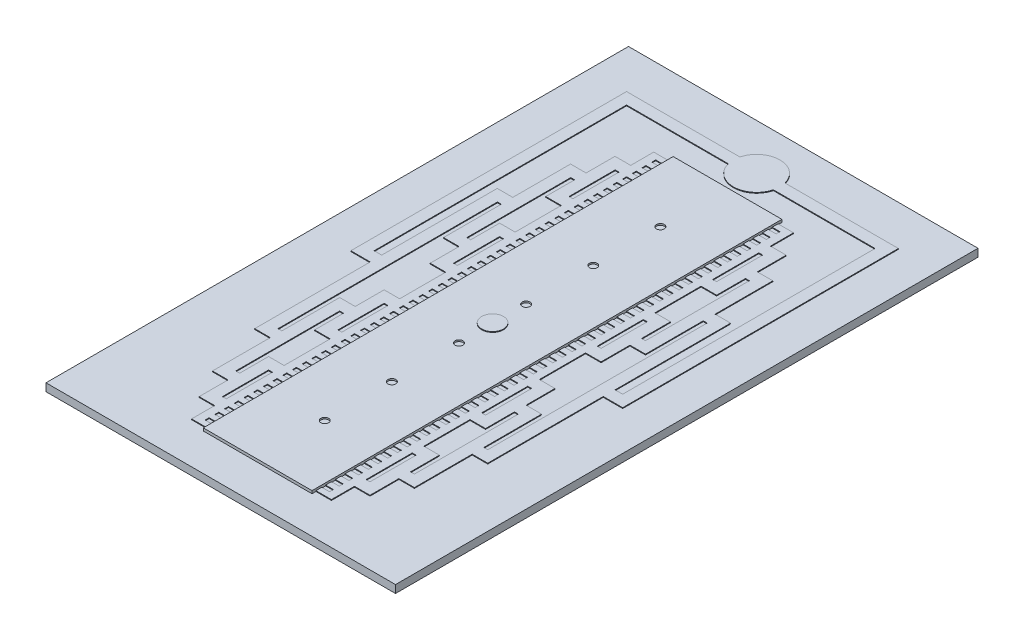
SolidWorks part; units mm, degrees
ref_plane "Front Plane" through (0, 0, 0) normal (0, 0, 1) x (1, 0, 0)
ref_plane "Top Plane" through (0, 0, 0) normal (0, 1, 0) x (1, 0, 0)
ref_plane "Right Plane" through (0, 0, 0) normal (1, 0, 0) x (0, 0, -1)
sketch "Sketch2" plane through (0, 0, 0) normal (0, 1, 0) x (1, 0, 0)
  line L1 (-22.5, 37.5) -> (22.5, 37.5)
  line L2 (-22.5, 37.5) -> (-22.5, -37.5)
  line L3 (-22.5, -37.5) -> (22.5, -37.5)
  line L4 (22.5, 37.5) -> (22.5, -37.5)
  line L5 (-22.5, 37.5) -> (22.5, -37.5) construction
  line L6 (-22.5, -37.5) -> (22.5, 37.5) construction
  point P0 (0, 0)
extrude "Boss-Extrude1" add sketch "Sketch2" along normal blind 1
sketch "Sketch3" plane through (0, 1, 0) normal (0, 1, 0) x (1, 0, 0)
  line L1 (-7, 30.25) -> (7, 30.25)
  line L2 (-7, 30.25) -> (-7, -30.25)
  line L3 (-7, -30.25) -> (7, -30.25)
  line L4 (7, 30.25) -> (7, -30.25)
  line L5 (-7, 30.25) -> (7, -30.25) construction
  line L6 (-7, -30.25) -> (7, 30.25) construction
  point P0 (0, 0)
extrude "Boss-Extrude2" add sketch "Sketch3" along normal blind 0.35
sketch "Sketch4" plane through (0, 1, 0) normal (0, 1, 0) x (1, 0, 0)
  line L0 (7, 29.75) -> (9, 29.75)
  line L1 (7, 29.75) -> (7, -29.75)
  line L2 (9, 29.75) -> (9, -29.75)
  line L3 (7, -29.75) -> (9, -29.75)
  line L4 (7, -30.25) -> (7, 30.25) construction
  line L5 (0, 31.7119) -> (0, -31.7119) construction
  line L6 (-9, 29.75) -> (-9, -29.75)
  line L7 (-7, -29.75) -> (-9, -29.75)
  line L8 (-7, 29.75) -> (-7, -29.75)
  line L9 (-7, 29.75) -> (-9, 29.75)
  point P6 (9, 0)
  point P11 (0, 0)
extrude "Boss-Extrude3" add sketch "Sketch4" along normal blind 0.1
sketch "Sketch5" plane through (0, 1.1, 0) normal (0, 1, 0) x (1, 0, 0)
  line L0 (7, 29) -> (8, 29)
  line L1 (7, 29) -> (7, 28.5)
  line L2 (8, 29) -> (8, 28.5)
  line L3 (7, 28.5) -> (8, 28.5)
  line L4 (7, -30.25) -> (7, 30.25) construction
  line L5 (-8, 29) -> (-7, 29)
  line L6 (-8, 29) -> (-8, 28.5)
  line L7 (-8, 28.5) -> (-7, 28.5)
  line L8 (-7, 29) -> (-7, 28.5)
  line L9 (-8, 27.75) -> (-7, 27.75)
  line L10 (-8, 27.75) -> (-8, 27.25)
  line L11 (-8, 27.25) -> (-7, 27.25)
  line L12 (-7, 27.75) -> (-7, 27.25)
  line L13 (-8, 26.5) -> (-7, 26.5)
  line L14 (-8, 26.5) -> (-8, 26)
  line L15 (-8, 26) -> (-7, 26)
  line L16 (-7, 26.5) -> (-7, 26)
  line L17 (-8, 25.25) -> (-7, 25.25)
  line L18 (-8, 25.25) -> (-8, 24.75)
  line L19 (-8, 24.75) -> (-7, 24.75)
  line L20 (-7, 25.25) -> (-7, 24.75)
  line L21 (-8, 24) -> (-7, 24)
  line L22 (-8, 24) -> (-8, 23.5)
  line L23 (-8, 23.5) -> (-7, 23.5)
  line L24 (-7, 24) -> (-7, 23.5)
  line L25 (-8, 22.75) -> (-7, 22.75)
  line L26 (-8, 22.75) -> (-8, 22.25)
  line L27 (-8, 22.25) -> (-7, 22.25)
  line L28 (-7, 22.75) -> (-7, 22.25)
  line L29 (-8, 21.5) -> (-7, 21.5)
  line L30 (-8, 21.5) -> (-8, 21)
  line L31 (-8, 21) -> (-7, 21)
  line L32 (-7, 21.5) -> (-7, 21)
  line L33 (-8, 20.25) -> (-7, 20.25)
  line L34 (-8, 20.25) -> (-8, 19.75)
  line L35 (-8, 19.75) -> (-7, 19.75)
  line L36 (-7, 20.25) -> (-7, 19.75)
  line L37 (-8, 19) -> (-7, 19)
  line L38 (-8, 19) -> (-8, 18.5)
  line L39 (-8, 18.5) -> (-7, 18.5)
  line L40 (-7, 19) -> (-7, 18.5)
  line L41 (-8, 17.75) -> (-7, 17.75)
  line L42 (-8, 17.75) -> (-8, 17.25)
  line L43 (-8, 17.25) -> (-7, 17.25)
  line L44 (-7, 17.75) -> (-7, 17.25)
  line L45 (-8, 16.5) -> (-7, 16.5)
  line L46 (-8, 16.5) -> (-8, 16)
  line L47 (-8, 16) -> (-7, 16)
  line L48 (-7, 16.5) -> (-7, 16)
  line L49 (-8, 15.25) -> (-7, 15.25)
  line L50 (-8, 15.25) -> (-8, 14.75)
  line L51 (-8, 14.75) -> (-7, 14.75)
  line L52 (-7, 15.25) -> (-7, 14.75)
  line L53 (-8, 14) -> (-7, 14)
  line L54 (-8, 14) -> (-8, 13.5)
  line L55 (-8, 13.5) -> (-7, 13.5)
  line L56 (-7, 14) -> (-7, 13.5)
  line L57 (-8, 12.75) -> (-7, 12.75)
  line L58 (-8, 12.75) -> (-8, 12.25)
  line L59 (-8, 12.25) -> (-7, 12.25)
  line L60 (-7, 12.75) -> (-7, 12.25)
  line L61 (-8, 11.5) -> (-7, 11.5)
  line L62 (-8, 11.5) -> (-8, 11)
  line L63 (-8, 11) -> (-7, 11)
  line L64 (-7, 11.5) -> (-7, 11)
  line L65 (-8, 10.25) -> (-7, 10.25)
  line L66 (-8, 10.25) -> (-8, 9.75)
  line L67 (-8, 9.75) -> (-7, 9.75)
  line L68 (-7, 10.25) -> (-7, 9.75)
  line L69 (-8, 9) -> (-7, 9)
  line L70 (-8, 9) -> (-8, 8.5)
  line L71 (-8, 8.5) -> (-7, 8.5)
  line L72 (-7, 9) -> (-7, 8.5)
  line L73 (-8, 7.75) -> (-7, 7.75)
  line L74 (-8, 7.75) -> (-8, 7.25)
  line L75 (-8, 7.25) -> (-7, 7.25)
  line L76 (-7, 7.75) -> (-7, 7.25)
  line L77 (-8, 6.5) -> (-7, 6.5)
  line L78 (-8, 6.5) -> (-8, 6)
  line L79 (-8, 6) -> (-7, 6)
  line L80 (-7, 6.5) -> (-7, 6)
  line L81 (-8, 5.25) -> (-7, 5.25)
  line L82 (-8, 5.25) -> (-8, 4.75)
  line L83 (-8, 4.75) -> (-7, 4.75)
  line L84 (-7, 5.25) -> (-7, 4.75)
  line L85 (-8, 4) -> (-7, 4)
  line L86 (-8, 4) -> (-8, 3.5)
  line L87 (-8, 3.5) -> (-7, 3.5)
  line L88 (-7, 4) -> (-7, 3.5)
  line L89 (-8, 2.75) -> (-7, 2.75)
  line L90 (-8, 2.75) -> (-8, 2.25)
  line L91 (-8, 2.25) -> (-7, 2.25)
  line L92 (-7, 2.75) -> (-7, 2.25)
  line L93 (-8, 1.5) -> (-7, 1.5)
  line L94 (-8, 1.5) -> (-8, 1)
  line L95 (-8, 1) -> (-7, 1)
  line L96 (-7, 1.5) -> (-7, 1)
  line L97 (-8, 0.25) -> (-7, 0.25)
  line L98 (-8, 0.25) -> (-8, -0.25)
  line L99 (-8, -0.25) -> (-7, -0.25)
  line L100 (-7, 0.25) -> (-7, -0.25)
  line L101 (-8, -1) -> (-7, -1)
  line L102 (-8, -1) -> (-8, -1.5)
  line L103 (-8, -1.5) -> (-7, -1.5)
  line L104 (-7, -1) -> (-7, -1.5)
  line L105 (-8, -2.25) -> (-7, -2.25)
  line L106 (-8, -2.25) -> (-8, -2.75)
  line L107 (-8, -2.75) -> (-7, -2.75)
  line L108 (-7, -2.25) -> (-7, -2.75)
  line L109 (-8, -3.5) -> (-7, -3.5)
  line L110 (-8, -3.5) -> (-8, -4)
  line L111 (-8, -4) -> (-7, -4)
  line L112 (-7, -3.5) -> (-7, -4)
  line L113 (-8, -4.75) -> (-7, -4.75)
  line L114 (-8, -4.75) -> (-8, -5.25)
  line L115 (-8, -5.25) -> (-7, -5.25)
  line L116 (-7, -4.75) -> (-7, -5.25)
  line L117 (-8, -6) -> (-7, -6)
  line L118 (-8, -6) -> (-8, -6.5)
  line L119 (-8, -6.5) -> (-7, -6.5)
  line L120 (-7, -6) -> (-7, -6.5)
  line L121 (-8, -7.25) -> (-7, -7.25)
  line L122 (-8, -7.25) -> (-8, -7.75)
  line L123 (-8, -7.75) -> (-7, -7.75)
  line L124 (-7, -7.25) -> (-7, -7.75)
  line L125 (-8, -8.5) -> (-7, -8.5)
  line L126 (-8, -8.5) -> (-8, -9)
  line L127 (-8, -9) -> (-7, -9)
  line L128 (-7, -8.5) -> (-7, -9)
  line L129 (-8, -9.75) -> (-7, -9.75)
  line L130 (-8, -9.75) -> (-8, -10.25)
  line L131 (-8, -10.25) -> (-7, -10.25)
  line L132 (-7, -9.75) -> (-7, -10.25)
  line L133 (-8, -11) -> (-7, -11)
  line L134 (-8, -11) -> (-8, -11.5)
  line L135 (-8, -11.5) -> (-7, -11.5)
  line L136 (-7, -11) -> (-7, -11.5)
  line L137 (-8, -12.25) -> (-7, -12.25)
  line L138 (-8, -12.25) -> (-8, -12.75)
  line L139 (-8, -12.75) -> (-7, -12.75)
  line L140 (-7, -12.25) -> (-7, -12.75)
  line L141 (-8, -13.5) -> (-7, -13.5)
  line L142 (-8, -13.5) -> (-8, -14)
  line L143 (-8, -14) -> (-7, -14)
  line L144 (-7, -13.5) -> (-7, -14)
  line L145 (-8, -14.75) -> (-7, -14.75)
  line L146 (-8, -14.75) -> (-8, -15.25)
  line L147 (-8, -15.25) -> (-7, -15.25)
  line L148 (-7, -14.75) -> (-7, -15.25)
  line L149 (-8, -16) -> (-7, -16)
  line L150 (-8, -16) -> (-8, -16.5)
  line L151 (-8, -16.5) -> (-7, -16.5)
  line L152 (-7, -16) -> (-7, -16.5)
  line L153 (-8, -17.25) -> (-7, -17.25)
  line L154 (-8, -17.25) -> (-8, -17.75)
  line L155 (-8, -17.75) -> (-7, -17.75)
  line L156 (-7, -17.25) -> (-7, -17.75)
  line L157 (-8, -18.5) -> (-7, -18.5)
  line L158 (-8, -18.5) -> (-8, -19)
  line L159 (-8, -19) -> (-7, -19)
  line L160 (-7, -18.5) -> (-7, -19)
  line L161 (-8, -19.75) -> (-7, -19.75)
  line L162 (-8, -19.75) -> (-8, -20.25)
  line L163 (-8, -20.25) -> (-7, -20.25)
  line L164 (-7, -19.75) -> (-7, -20.25)
  line L165 (-8, -21) -> (-7, -21)
  line L166 (-8, -21) -> (-8, -21.5)
  line L167 (-8, -21.5) -> (-7, -21.5)
  line L168 (-7, -21) -> (-7, -21.5)
  line L169 (-8, -22.25) -> (-7, -22.25)
  line L170 (-8, -22.25) -> (-8, -22.75)
  line L171 (-8, -22.75) -> (-7, -22.75)
  line L172 (-7, -22.25) -> (-7, -22.75)
  line L173 (-8, -23.5) -> (-7, -23.5)
  line L174 (-8, -23.5) -> (-8, -24)
  line L175 (-8, -24) -> (-7, -24)
  line L176 (-7, -23.5) -> (-7, -24)
  line L177 (-8, -24.75) -> (-7, -24.75)
  line L178 (-8, -24.75) -> (-8, -25.25)
  line L179 (-8, -25.25) -> (-7, -25.25)
  line L180 (-7, -24.75) -> (-7, -25.25)
  line L181 (-8, -26) -> (-7, -26)
  line L182 (-8, -26) -> (-8, -26.5)
  line L183 (-8, -26.5) -> (-7, -26.5)
  line L184 (-7, -26) -> (-7, -26.5)
  line L185 (-8, -27.25) -> (-7, -27.25)
  line L186 (-8, -27.25) -> (-8, -27.75)
  line L187 (-8, -27.75) -> (-7, -27.75)
  line L188 (-7, -27.25) -> (-7, -27.75)
  line L189 (-8, -28.5) -> (-7, -28.5)
  line L190 (-8, -28.5) -> (-8, -29)
  line L191 (-8, -29) -> (-7, -29)
  line L192 (-7, -28.5) -> (-7, -29)
  line L193 (7, 27.75) -> (8, 27.75)
  line L194 (7, 27.75) -> (7, 27.25)
  line L195 (7, 27.25) -> (8, 27.25)
  line L196 (8, 27.75) -> (8, 27.25)
  line L197 (7, 26.5) -> (8, 26.5)
  line L198 (7, 26.5) -> (7, 26)
  line L199 (7, 26) -> (8, 26)
  line L200 (8, 26.5) -> (8, 26)
  line L201 (7, 25.25) -> (8, 25.25)
  line L202 (7, 25.25) -> (7, 24.75)
  line L203 (7, 24.75) -> (8, 24.75)
  line L204 (8, 25.25) -> (8, 24.75)
  line L205 (7, 24) -> (8, 24)
  line L206 (7, 24) -> (7, 23.5)
  line L207 (7, 23.5) -> (8, 23.5)
  line L208 (8, 24) -> (8, 23.5)
  line L209 (7, 22.75) -> (8, 22.75)
  line L210 (7, 22.75) -> (7, 22.25)
  line L211 (7, 22.25) -> (8, 22.25)
  line L212 (8, 22.75) -> (8, 22.25)
  line L213 (7, 21.5) -> (8, 21.5)
  line L214 (7, 21.5) -> (7, 21)
  line L215 (7, 21) -> (8, 21)
  line L216 (8, 21.5) -> (8, 21)
  line L217 (7, 20.25) -> (8, 20.25)
  line L218 (7, 20.25) -> (7, 19.75)
  line L219 (7, 19.75) -> (8, 19.75)
  line L220 (8, 20.25) -> (8, 19.75)
  line L221 (7, 19) -> (8, 19)
  line L222 (7, 19) -> (7, 18.5)
  line L223 (7, 18.5) -> (8, 18.5)
  line L224 (8, 19) -> (8, 18.5)
  line L225 (7, 17.75) -> (8, 17.75)
  line L226 (7, 17.75) -> (7, 17.25)
  line L227 (7, 17.25) -> (8, 17.25)
  line L228 (8, 17.75) -> (8, 17.25)
  line L229 (7, 16.5) -> (8, 16.5)
  line L230 (7, 16.5) -> (7, 16)
  line L231 (7, 16) -> (8, 16)
  line L232 (8, 16.5) -> (8, 16)
  line L233 (7, 15.25) -> (8, 15.25)
  line L234 (7, 15.25) -> (7, 14.75)
  line L235 (7, 14.75) -> (8, 14.75)
  line L236 (8, 15.25) -> (8, 14.75)
  line L237 (7, 14) -> (8, 14)
  line L238 (7, 14) -> (7, 13.5)
  line L239 (7, 13.5) -> (8, 13.5)
  line L240 (8, 14) -> (8, 13.5)
  line L241 (7, 12.75) -> (8, 12.75)
  line L242 (7, 12.75) -> (7, 12.25)
  line L243 (7, 12.25) -> (8, 12.25)
  line L244 (8, 12.75) -> (8, 12.25)
  line L245 (7, 11.5) -> (8, 11.5)
  line L246 (7, 11.5) -> (7, 11)
  line L247 (7, 11) -> (8, 11)
  line L248 (8, 11.5) -> (8, 11)
  line L249 (7, 10.25) -> (8, 10.25)
  line L250 (7, 10.25) -> (7, 9.75)
  line L251 (7, 9.75) -> (8, 9.75)
  line L252 (8, 10.25) -> (8, 9.75)
  line L253 (7, 9) -> (8, 9)
  line L254 (7, 9) -> (7, 8.5)
  line L255 (7, 8.5) -> (8, 8.5)
  line L256 (8, 9) -> (8, 8.5)
  line L257 (7, 7.75) -> (8, 7.75)
  line L258 (7, 7.75) -> (7, 7.25)
  line L259 (7, 7.25) -> (8, 7.25)
  line L260 (8, 7.75) -> (8, 7.25)
  line L261 (7, 6.5) -> (8, 6.5)
  line L262 (7, 6.5) -> (7, 6)
  line L263 (7, 6) -> (8, 6)
  line L264 (8, 6.5) -> (8, 6)
  line L265 (7, 5.25) -> (8, 5.25)
  line L266 (7, 5.25) -> (7, 4.75)
  line L267 (7, 4.75) -> (8, 4.75)
  line L268 (8, 5.25) -> (8, 4.75)
  line L269 (7, 4) -> (8, 4)
  line L270 (7, 4) -> (7, 3.5)
  line L271 (7, 3.5) -> (8, 3.5)
  line L272 (8, 4) -> (8, 3.5)
  line L273 (7, 2.75) -> (8, 2.75)
  line L274 (7, 2.75) -> (7, 2.25)
  line L275 (7, 2.25) -> (8, 2.25)
  line L276 (8, 2.75) -> (8, 2.25)
  line L277 (7, 1.5) -> (8, 1.5)
  line L278 (7, 1.5) -> (7, 1)
  line L279 (7, 1) -> (8, 1)
  line L280 (8, 1.5) -> (8, 1)
  line L281 (7, 0.25) -> (8, 0.25)
  line L282 (7, 0.25) -> (7, -0.25)
  line L283 (7, -0.25) -> (8, -0.25)
  line L284 (8, 0.25) -> (8, -0.25)
  line L285 (7, -1) -> (8, -1)
  line L286 (7, -1) -> (7, -1.5)
  line L287 (7, -1.5) -> (8, -1.5)
  line L288 (8, -1) -> (8, -1.5)
  line L289 (7, -2.25) -> (8, -2.25)
  line L290 (7, -2.25) -> (7, -2.75)
  line L291 (7, -2.75) -> (8, -2.75)
  line L292 (8, -2.25) -> (8, -2.75)
  line L293 (7, -3.5) -> (8, -3.5)
  line L294 (7, -3.5) -> (7, -4)
  line L295 (7, -4) -> (8, -4)
  line L296 (8, -3.5) -> (8, -4)
  line L297 (7, -4.75) -> (8, -4.75)
  line L298 (7, -4.75) -> (7, -5.25)
  line L299 (7, -5.25) -> (8, -5.25)
  line L300 (8, -4.75) -> (8, -5.25)
  line L301 (7, -6) -> (8, -6)
  line L302 (7, -6) -> (7, -6.5)
  line L303 (7, -6.5) -> (8, -6.5)
  line L304 (8, -6) -> (8, -6.5)
  line L305 (7, -7.25) -> (8, -7.25)
  line L306 (7, -7.25) -> (7, -7.75)
  line L307 (7, -7.75) -> (8, -7.75)
  line L308 (8, -7.25) -> (8, -7.75)
  line L309 (7, -8.5) -> (8, -8.5)
  line L310 (7, -8.5) -> (7, -9)
  line L311 (7, -9) -> (8, -9)
  line L312 (8, -8.5) -> (8, -9)
  line L313 (7, -9.75) -> (8, -9.75)
  line L314 (7, -9.75) -> (7, -10.25)
  line L315 (7, -10.25) -> (8, -10.25)
  line L316 (8, -9.75) -> (8, -10.25)
  line L317 (7, -11) -> (8, -11)
  line L318 (7, -11) -> (7, -11.5)
  line L319 (7, -11.5) -> (8, -11.5)
  line L320 (8, -11) -> (8, -11.5)
  line L321 (7, -12.25) -> (8, -12.25)
  line L322 (7, -12.25) -> (7, -12.75)
  line L323 (7, -12.75) -> (8, -12.75)
  line L324 (8, -12.25) -> (8, -12.75)
  line L325 (7, -13.5) -> (8, -13.5)
  line L326 (7, -13.5) -> (7, -14)
  line L327 (7, -14) -> (8, -14)
  line L328 (8, -13.5) -> (8, -14)
  line L329 (7, -14.75) -> (8, -14.75)
  line L330 (7, -14.75) -> (7, -15.25)
  line L331 (7, -15.25) -> (8, -15.25)
  line L332 (8, -14.75) -> (8, -15.25)
  line L333 (7, -16) -> (8, -16)
  line L334 (7, -16) -> (7, -16.5)
  line L335 (7, -16.5) -> (8, -16.5)
  line L336 (8, -16) -> (8, -16.5)
  line L337 (7, -17.25) -> (8, -17.25)
  line L338 (7, -17.25) -> (7, -17.75)
  line L339 (7, -17.75) -> (8, -17.75)
  line L340 (8, -17.25) -> (8, -17.75)
  line L341 (7, -18.5) -> (8, -18.5)
  line L342 (7, -18.5) -> (7, -19)
  line L343 (7, -19) -> (8, -19)
  line L344 (8, -18.5) -> (8, -19)
  line L345 (7, -19.75) -> (8, -19.75)
  line L346 (7, -19.75) -> (7, -20.25)
  line L347 (7, -20.25) -> (8, -20.25)
  line L348 (8, -19.75) -> (8, -20.25)
  line L349 (7, -21) -> (8, -21)
  line L350 (7, -21) -> (7, -21.5)
  line L351 (7, -21.5) -> (8, -21.5)
  line L352 (8, -21) -> (8, -21.5)
  line L353 (7, -22.25) -> (8, -22.25)
  line L354 (7, -22.25) -> (7, -22.75)
  line L355 (7, -22.75) -> (8, -22.75)
  line L356 (8, -22.25) -> (8, -22.75)
  line L357 (7, -23.5) -> (8, -23.5)
  line L358 (7, -23.5) -> (7, -24)
  line L359 (7, -24) -> (8, -24)
  line L360 (8, -23.5) -> (8, -24)
  line L361 (7, -24.75) -> (8, -24.75)
  line L362 (7, -24.75) -> (7, -25.25)
  line L363 (7, -25.25) -> (8, -25.25)
  line L364 (8, -24.75) -> (8, -25.25)
  line L365 (7, -26) -> (8, -26)
  line L366 (7, -26) -> (7, -26.5)
  line L367 (7, -26.5) -> (8, -26.5)
  line L368 (8, -26) -> (8, -26.5)
  line L369 (7, -27.25) -> (8, -27.25)
  line L370 (7, -27.25) -> (7, -27.75)
  line L371 (7, -27.75) -> (8, -27.75)
  line L372 (8, -27.25) -> (8, -27.75)
  line L373 (7, -28.5) -> (8, -28.5)
  line L374 (7, -28.5) -> (7, -29)
  line L375 (7, -29) -> (8, -29)
  line L376 (8, -28.5) -> (8, -29)
  dimension "D1" = 0.75
  dimension "D2" = 2
  dimension "D3" = 47
extrude "Cut-Extrude1" cut sketch "Sketch5" against normal blind 0.1
sketch "Sketch6" plane through (0, 1, 0) normal (0, 1, 0) x (1, 0, 0)
  line L0 (0, -32.9565) -> (0, 32.9565) construction
  line L1 (-17.9872, 0) -> (17.9872, 0) construction
  line L2 (7, 30.25) -> (-7, 30.25) construction
  line L3 (-17.5, 34.75) -> (17.5, 34.75)
  line L4 (-16, 33.25) -> (16, 33.25)
  line L5 (-17.5, 34.75) -> (-17.5, -0.75)
  line L6 (-16, 33.25) -> (-16, 0.75)
  line L7 (-17.5, -0.75) -> (-15, -0.75)
  line L8 (-16, 0.75) -> (-15.0229, 0.75)
  line L9 (-9, 29.75) -> (-9, -29.75) construction
  line L10 (-9, 26.7813) -> (-11.0229, 26.7813)
  line L11 (-9, 25.2813) -> (-9.5, 25.2813)
  line L12 (-9, 17.8438) -> (-11, 17.8438)
  line L13 (-9, 19.3438) -> (-9.5, 19.3438)
  line L14 (-9.5, 19.3438) -> (-9.5, 25.2813)
  line L15 (-11.0229, 23.0625) -> (-11.0229, 26.7813)
  line L16 (-11, 21.5625) -> (-11, 17.8438)
  line L17 (-9, 29.75) -> (-9, -29.75) construction
  line L18 (-9, 2.9688) -> (-11, 2.9688)
  line L19 (-9, 4.4688) -> (-9.5, 4.4688)
  line L20 (-9, 11.9063) -> (-11, 11.9063)
  line L21 (-9, 10.4063) -> (-9.5, 10.4063)
  line L22 (-9.5, 10.4063) -> (-9.5, 4.4688)
  line L23 (-11, 2.9688) -> (-11, 6.6875)
  line L24 (-11, 8.1875) -> (-11, 11.9063)
  line L25 (-9, -2.9687) -> (-11, -2.9687)
  line L26 (-9, -4.4687) -> (-9.5, -4.4687)
  line L27 (-9, -11.9062) -> (-11, -11.9062)
  line L28 (-9, -10.4062) -> (-9.5, -10.4062)
  line L29 (-9.5, -10.4062) -> (-9.5, -4.4687)
  line L30 (-11, -11.9062) -> (-11, -8.1875)
  line L31 (-9, -17.8437) -> (-11, -17.8437)
  line L32 (-11, -6.6875) -> (-11, -2.9687)
  line L33 (-9, -19.3437) -> (-9.5, -19.3437)
  line L34 (-9, -26.7812) -> (-11, -26.7812)
  line L35 (-9, -25.2812) -> (-9.5, -25.2812)
  line L36 (-9.5, -25.2812) -> (-9.5, -19.3437)
  line L37 (-11, -17.8437) -> (-11, -21.5625)
  line L38 (-11, -23.0625) -> (-11, -26.7812)
  line L39 (-9, -22.3125) -> (-11.344, -22.3125) construction
  line L40 (-9, -7.4375) -> (-11.3125, -7.4375) construction
  line L41 (-9, 7.4375) -> (-11.3125, 7.4375) construction
  line L42 (-9, 22.3125) -> (-11.3125, 22.3125) construction
  line L43 (-11.0229, 23.0625) -> (-13.0229, 23.0625)
  line L44 (-11, 21.5625) -> (-11.5, 21.5625)
  line L45 (-11, 6.6875) -> (-13, 6.6875)
  line L46 (-11, 8.1875) -> (-11.5, 8.1875)
  line L47 (-11.5, 8.1875) -> (-11.5, 21.5625)
  line L48 (-13.0229, 23.0625) -> (-13.0229, 15.625)
  line L49 (-13, 14.125) -> (-13, 6.6875)
  line L50 (-11, -6.6875) -> (-13, -6.6875)
  line L51 (-11, -8.1875) -> (-11.5, -8.1875)
  line L52 (-11, -23.0625) -> (-13, -23.0625)
  line L53 (-11, -21.5625) -> (-11.5, -21.5625)
  line L54 (-11.5, -21.5625) -> (-11.5, -8.1875)
  line L55 (-13, -6.6875) -> (-13, -14.125)
  line L56 (-13, -15.625) -> (-13, -23.0625)
  line L57 (-9, 14.875) -> (-13.3781, 14.875) construction
  line L58 (-9, -14.875) -> (-13.151, -14.875) construction
  line L59 (-13, -15.625) -> (-15, -15.625)
  line L60 (-13, -14.125) -> (-13.5, -14.125)
  line L61 (-13.0229, 15.625) -> (-15.0229, 15.625)
  line L62 (-13, 14.125) -> (-13.5, 14.125)
  line L63 (-13.5, 14.125) -> (-13.5, -14.125)
  line L64 (-15, -15.625) -> (-15, -0.75)
  line L65 (-15.0229, 0.75) -> (-15.0229, 15.625)
  line L66 (9, 25.2813) -> (9.5, 25.2813)
  line L67 (11.0229, 23.0625) -> (11.0229, 26.7813)
  line L68 (9, 26.7813) -> (11.0229, 26.7813)
  line L69 (11.0229, 23.0625) -> (13.0229, 23.0625)
  line L70 (11, 21.5625) -> (11.5, 21.5625)
  line L71 (9.5, 19.3438) -> (9.5, 25.2813)
  line L72 (9, 19.3438) -> (9.5, 19.3438)
  line L73 (11, 21.5625) -> (11, 17.8438)
  line L74 (9, 17.8438) -> (11, 17.8438)
  line L75 (13.0229, 23.0625) -> (13.0229, 15.625)
  line L76 (13, 14.125) -> (13.5, 14.125)
  line L77 (13.0229, 15.625) -> (15.0229, 15.625)
  line L78 (9, 10.4063) -> (9.5, 10.4063)
  line L79 (9, 11.9063) -> (11, 11.9063)
  line L80 (11, 8.1875) -> (11, 11.9063)
  line L81 (11.5, 8.1875) -> (11.5, 21.5625)
  line L82 (11, 8.1875) -> (11.5, 8.1875)
  line L83 (13, 14.125) -> (13, 6.6875)
  line L84 (11, 6.6875) -> (13, 6.6875)
  line L85 (9, 4.4688) -> (9.5, 4.4688)
  line L86 (9.5, 10.4063) -> (9.5, 4.4688)
  line L87 (11, 2.9688) -> (11, 6.6875)
  line L88 (9, 2.9688) -> (11, 2.9688)
  line L89 (17.5, 34.75) -> (17.5, -0.75)
  line L90 (15.0229, 0.75) -> (15.0229, 15.625)
  line L91 (16, 33.25) -> (16, 0.75)
  line L92 (16, 0.75) -> (15.0229, 0.75)
  line L93 (17.5, -0.75) -> (15, -0.75)
  line L94 (9, -2.9687) -> (11, -2.9687)
  line L95 (9, -10.4062) -> (9.5, -10.4062)
  line L96 (9, -4.4687) -> (9.5, -4.4687)
  line L97 (11, -6.6875) -> (11, -2.9687)
  line L98 (11, -6.6875) -> (13, -6.6875)
  line L99 (11, -8.1875) -> (11.5, -8.1875)
  line L100 (9.5, -10.4062) -> (9.5, -4.4687)
  line L101 (11, -11.9062) -> (11, -8.1875)
  line L102 (9, -11.9062) -> (11, -11.9062)
  line L103 (13, -6.6875) -> (13, -14.125)
  line L104 (15, -15.625) -> (15, -0.75)
  line L105 (13.5, 14.125) -> (13.5, -14.125)
  line L106 (13, -15.625) -> (15, -15.625)
  line L107 (13, -14.125) -> (13.5, -14.125)
  line L108 (9, -17.8437) -> (11, -17.8437)
  line L109 (9, -19.3437) -> (9.5, -19.3437)
  line L110 (11, -17.8437) -> (11, -21.5625)
  line L111 (11.5, -21.5625) -> (11.5, -8.1875)
  line L112 (13, -15.625) -> (13, -23.0625)
  line L113 (11, -23.0625) -> (13, -23.0625)
  line L114 (11, -21.5625) -> (11.5, -21.5625)
  line L115 (9.5, -25.2812) -> (9.5, -19.3437)
  line L116 (11, -23.0625) -> (11, -26.7812)
  line L117 (9, -26.7812) -> (11, -26.7812)
  line L118 (9, -25.2812) -> (9.5, -25.2812)
  circle A0 centre (0, 34) radius 3
  point P0 (0, 30.25)
  point P4 (0, 0)
  point P8 (0, 0)
  point P9 (0, 34)
  point P14 (0, 33.25)
  point P15 (0, 34.75)
  point P16 (-16, 0)
  point P19 (0, 34.75)
  point P22 (0, 33.25)
  point P24 (-17.5, 0)
  point P26 (-9, 29.75)
  point P29 (-9, 26.7813)
  point P31 (-9, 25.2813)
  point P32 (-9, 26.0313)
  point P33 (-9, 22.3125)
  point P34 (-9, 18.5938)
  point P35 (-9, 14.875)
  point P36 (-9, 11.1563)
  point P37 (-9, 7.4375)
  point P38 (-9, 3.7188)
  point P39 (-9, 0)
  point P40 (-9, -3.7187)
  point P41 (-9, -7.4375)
  point P42 (-9, -11.1562)
  point P43 (-9, -14.875)
  point P44 (-9, -18.5937)
  point P45 (-9, -22.3125)
  point P46 (-9, -26.0312)
  point P47 (-9, -29.75)
  point P54 (-9, 19.3438)
  point P55 (-9, 17.8438)
  point P65 (-9, 11.9063)
  point P66 (-9, 10.4063)
  point P69 (-9, 4.4688)
  point P70 (-9, 2.9688)
  point P81 (-9, -2.9687)
  point P82 (-9, -4.4687)
  point P87 (-9, -10.4062)
  point P88 (-9, -11.9062)
  point P93 (-9, -17.8437)
  point P96 (-9, -19.3437)
  point P101 (-9, -25.2812)
  point P102 (-9, -26.7812)
  point P125 (-11, -7.4375)
  point P126 (-11, -22.3125)
  point P137 (-13, -14.875)
  line M5 (-9, -29.75) -> (-9, 29.75)
  line M11 (9, 29.75) -> (9, -29.75)
  dimension "D2" = 0.75
  dimension "D4" = 0.75
  dimension "D5" = 0.75
  dimension "D1" = 3.75
  dimension "D3" = 0.75
  dimension "D6" = 17
  dimension "D7" = 0.75
  dimension "D8" = 0.75
  dimension "D9" = 0.75
  dimension "D10" = 0.75
  dimension "D11" = 0.75
  dimension "D12" = 0.75
  dimension "D13" = 0.75
  dimension ".75" = 0.75
  dimension "D14" = 0.75
  dimension "D15" = 0.75
  dimension "D16" = 0.75
  dimension "D17" = 0.75
  dimension "D18" = 0.75
  dimension "D19" = 0.75
  dimension "D20" = 0.75
  dimension "D21" = 0.75
extrude "Boss-Extrude4" add sketch "Sketch6" along normal blind 0.1 contours A0 L4 L91 L92 L90 L77 L75 L69 L67 L68 L66 L71 L72 L74 L73 L70 L81 L82 L80 L79 L78 L86 L85 L88 L87 L84 L83 L76 L105 L107 L103 L98 L97 L94 L96 L100 L95 L102 L101 L99 L111 L114 L110 L108 M11 | A0 L3 L5 L7 L64 L59 L56 L52 L38 L34 L35 L36 L33 L31 L37 L53 L54 L51 L30 L27 L28 L29 L26 L25 L32 L50 L55 L60 L63 L62 L49 L45 L23 L18 L19 L22 L21 L20 L24 L46 L47 L44 L16 L12 M5 | L4 A0 L3 | L3 A0 | L4 A0 region at (-12.924, 1, -6.7147) region at (0, 1, -35.6871) region at (0, 1, -34) region at (12.924, 1, -6.7147) region at (0, 1, -32.3129)
sketch "Sketch7" plane through (0, 1.35, 0) normal (0, 1, 0) x (1, 0, 0)
  circle A0 centre (0, 0) radius 1.4
extrude "Boss-Extrude5" add sketch "Sketch7" along normal blind 0.1
sketch "Sketch8" plane through (0, 1.35, 0) normal (0, 1, 0) x (1, 0, 0)
  line L0 (0, 29.6213) -> (0, -29.6213) construction
  line L1 (7, 30.25) -> (-7, 30.25) construction
  circle A0 centre (0, 21.6071) radius 0.5
  circle A1 centre (0, 12.9643) radius 0.5
  circle A2 centre (0, 4.3214) radius 0.5
  circle A3 centre (0, -4.3214) radius 0.5
  circle A4 centre (0, -12.9643) radius 0.5
  circle A5 centre (0, -21.6071) radius 0.5
  point P0 (0, 21.6071)
  point P5 (0, 0)
  point P7 (0, 30.25)
  dimension "D2" = 6
  dimension "D1" = 8.6429
extrude "Cut-Extrude2" cut sketch "Sketch8" against normal blind 0.2
sketch "Sketch9" plane through (0, 0, 37.5) normal (0, 0, 1) x (1, 0, 0)
  line L0 (22.5, 1) -> (22.5, 0)
  line L1 (22.5, 1) -> (-22.5037, 1)
  line L2 (22.5, 0) -> (-22.5037, 0)
  line L3 (-22.5037, 1) -> (-22.5037, 0)
extrude "Cut-Extrude3" cut sketch "Sketch9" against normal blind 2.5
sketch "Sketch10" plane through (0, 0, -37.5) normal (0, 0, -1) x (-1, 0, 0)
  line L0 (-22.5, 1) -> (-22.5, 0)
  line L1 (-22.5, 1) -> (22.5017, 1)
  line L2 (-22.5, 0) -> (22.5017, 0)
  line L3 (22.5017, 1) -> (22.5017, 0)
extrude "Boss-Extrude6" add sketch "Sketch10" along normal blind 2.5
